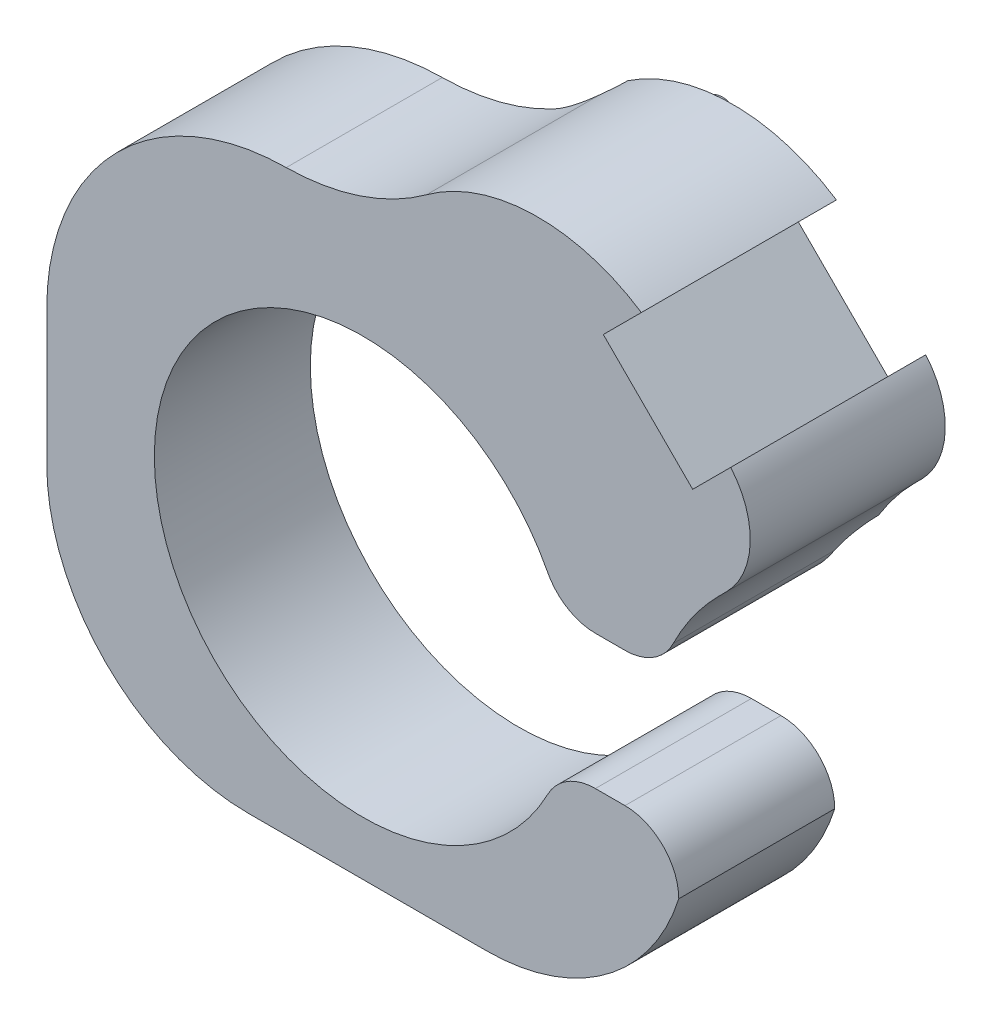
SolidWorks part; units mm, degrees
ref_plane "Front Plane" through (0, 0, 0) normal (0, 0, 1) x (1, 0, 0)
ref_plane "Top Plane" through (0, 0, 0) normal (0, 1, 0) x (1, 0, 0)
ref_plane "Right Plane" through (0, 0, 0) normal (1, 0, 0) x (0, 0, -1)
sketch "Sketch1" plane through (0, 0, 0) normal (0, 0, 1) x (1, 0, 0)
  line L0 (0, 9.25) -> (0, -12.25) construction
  line L2 (-11.75, 9.25) -> (-11.75, -10.25)
  line L3 (-9.75, -12.25) -> (9.75, -12.25)
  line L4 (11.75, 9.25) -> (11.75, 2)
  line L8 (0, -2.5) -> (11.75, -2.5) construction
  line L10 (-11.75, -10.25) -> (-11.75, -12.25)
  line L11 (-11.75, -12.25) -> (-9.75, -12.25)
  line L14 (11.75, 0) -> (13.7578, 0) construction
  line L15 (9.75, 0) -> (8.6494, 0)
  line L16 (9.75, -5) -> (8.6494, -5)
  line L17 (11.75, -7) -> (11.75, -10.25)
  line L20 (11.75, -10.25) -> (11.75, -12.25)
  line L21 (11.75, -12.25) -> (9.75, -12.25)
  line L25 (-11.75, 9.25) -> (11.75, 9.25)
  arc A0 (6.8752, 1.0769) -> (6.8752, -6.0769) centre (0, -2.5) ccw
  arc A1 (6.8752, 1.0769) -> (8.6494, 0) centre (8.6494, 2) ccw
  arc A2 (6.8752, -6.0769) -> (8.6494, -5) centre (8.6494, -7) cw
  arc A3 (9.75, -5) -> (11.75, -7) centre (9.75, -7) cw
  arc A4 (11.75, 2) -> (9.75, 0) centre (9.75, 2) cw
  point P0 (0, 0)
  point P27 (11.75, -5)
  point P45 (0, 10.25)
  dimension "D6" = 15.5
  dimension "D8" = 2
  dimension "D4" = 11.75
  dimension "D7" = 2.5
extrude "Boss-Extrude1" add sketch "Sketch1" along normal blind 5.8
sketch "Sketch3" plane through (0, 0, 5.8) normal (0, 0, 1) x (1, 0, 0)
  line L0 (-1.4053, 7.0549) -> (6.5407, 15.0009)
  line L2 (6.5407, 15.0009) -> (17.5009, 4.0407)
  line L4 (12.0208, 9.5208) -> (0, -2.5) construction
  line L5 (0.1768, 8.6369) -> (11.1369, -2.3232) construction
  line L6 (17.5009, 4.0407) -> (11.75, 2)
  line L7 (11.75, 2) -> (-1.4053, 7.0549)
  point P1 (5.6569, 3.1569)
  dimension "D1" = 17
extrude "Boss-Extrude2" add sketch "Sketch3" against normal blind 5.8 contours L7 L0 L2 L6
sketch "Sketch5" plane through (0, 0, 5.8) normal (0, 0, 1) x (1, 0, 0)
  line L0 (11.75, 2) -> (2.6449, 11.1051)
  line L1 (-1.4053, 7.0549) -> (6.5407, 15.0009) construction
  line L3 (2.6449, 11.1051) -> (6.5407, 15.0009)
  line L4 (6.5407, 15.0009) -> (17.5009, 4.0407)
  line L5 (17.5009, 4.0407) -> (11.75, 2)
extrude "Boss-Extrude3" add sketch "Sketch5" against normal blind 10.3
sketch "Sketch6" plane through (0, 0, 5.8) normal (0, 0, 1) x (1, 0, 0)
  line L0 (8.9449, 9.7683) -> (10.3591, 11.1825)
  line L1 (8.9449, 9.7683) -> (12.2683, 6.4449)
  line L2 (10.3591, 11.1825) -> (13.6825, 7.8591)
  line L3 (12.2683, 6.4449) -> (13.6825, 7.8591)
  line L4 (12.0208, 9.5208) -> (10.6066, 8.1066) construction
  line L5 (9.652, 10.4754) -> (12.9754, 7.152) construction
  line L6 (6.5407, 15.0009) -> (17.5009, 4.0407) construction
  point P1 (11.3137, 8.8137)
  dimension "D1" = 2
  dimension "D2" = 4.7
extrude "Cut-Extrude2" cut sketch "Sketch6" against normal blind 10.3
fillet "Fillet6" radius 9 1 edges at (-11.75, 9.25, 2.9)
fillet "Fillet7" radius 7.5 1 edges at (-11.75, -12.25, 2.9)
fillet "Fillet8" radius 7.5 1 edges at (11.75, -12.25, 2.9)
fillet "Fillet14" radius 9 1 edges at (0.7898, 9.25, 2.9)
fillet "Fillet15" radius 7 1 edges at (6.5407, 15.0009, 0.65)
fillet "Fillet18" radius 1.5 1 edges at (7.177, 6.573, 0)
sketch "Sketch9" plane through (0, 0, 5.8) normal (0, 0, 1) x (1, 0, 0)
  line L0 (11.75, 2) -> (16.3624, 6.6124)
  line L1 (6.5407, 15.0009) -> (17.5009, 4.0407) construction
  line L2 (16.3624, 6.6124) -> (17.5009, 4.0407)
  line L3 (17.5009, 4.0407) -> (11.75, 2)
extrude "Cut-Extrude4" cut sketch "Sketch9" against normal blind 10.3
fillet "Fillet19" radius 3 1 edges at (15.6458, 5.8958, 0.65)
fillet "Fillet20" radius 9 1 edges at (11.75, 2, 2.15)
sketch "Sketch10" plane through (0, 0, -4.5) normal (0, 0, -1) x (-1, 0, 0)
  line L1 (-24.3054, -2.6529) -> (5.5055, -2.6529)
  line L2 (-24.3054, -2.6529) -> (-24.3054, 17.3185)
  line L3 (-24.3054, 17.3185) -> (5.5055, 17.3185)
  line L4 (5.5055, -2.6529) -> (5.5055, 17.3185)
extrude "Cut-Extrude5" cut sketch "Sketch10" against normal blind 3.048
sketch "Sketch11" plane through (0, 0, -1.452) normal (0, 0, -1) x (-1, 0, 0)
  text T0 "FR " font "Century Gothic" height in points 11
extrude "Boss-Extrude4" add sketch "Sketch11" along normal blind 0.508
